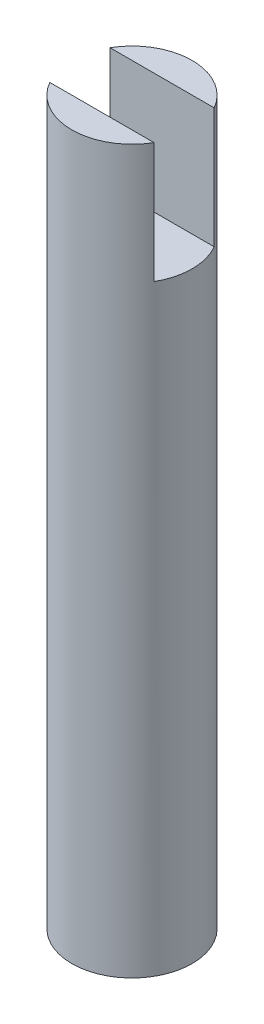
SolidWorks part; units mm, degrees
ref_plane "Front Plane" through (0, 0, 0) normal (0, 0, 1) x (1, 0, 0)
ref_plane "Top Plane" through (0, 0, 0) normal (0, 1, 0) x (1, 0, 0)
ref_plane "Right Plane" through (0, 0, 0) normal (1, 0, 0) x (0, 0, -1)
sketch "Sketch1" plane through (0, 0, 0) normal (0, 1, 0) x (1, 0, 0)
  circle A0 centre (0, 0) radius 25.4
  dimension "D1" = 50.8
extrude "Boss-Extrude1" add sketch "Sketch1" along normal blind 25.4 and the other way blind 279.4 contours A0
sketch "Sketch3" plane through (0, 0, 0) normal (1, 0, 0) x (0, 0, -1)
  line L0 (25.4, 25.4) -> (-25.4, 25.4) construction
  line L1 (-12.7, 25.4) -> (12.7, 25.4)
  line L2 (-12.7, 25.4) -> (-12.7, -25.4)
  line L3 (-12.7, -25.4) -> (12.7, -25.4)
  line L4 (12.7, 25.4) -> (12.7, -25.4)
  line L5 (-25.4, 25.4) -> (-25.4, -279.4) construction
  dimension "D1" = 50.8
  dimension "D2" = 25.4
  dimension "D3" = 12.7
extrude "Cut-Extrude2" cut sketch "Sketch3" against normal through all both and the other way through all
